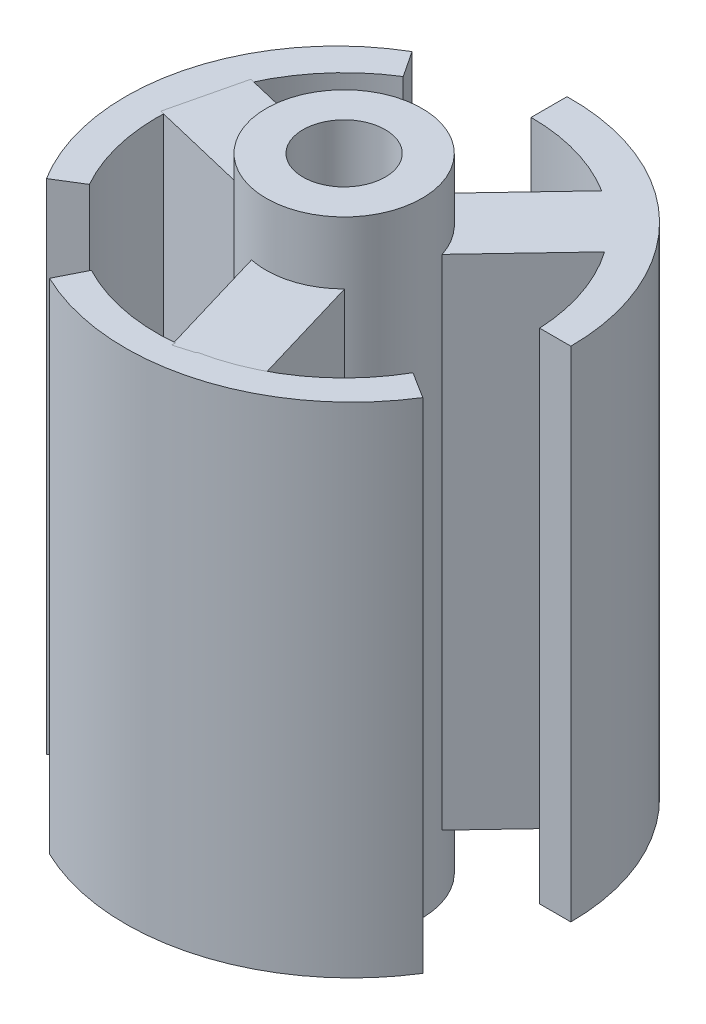
SolidWorks part; units mm, degrees
ref_plane "Front Plane" through (0, 0, 0) normal (0, 0, 1) x (1, 0, 0)
ref_plane "Top Plane" through (0, 0, 0) normal (0, 1, 0) x (1, 0, 0)
ref_plane "Right Plane" through (0, 0, 0) normal (1, 0, 0) x (0, 0, -1)
sketch "Sketch11" plane through (0, 0, 0) normal (0, 1, 0) x (1, 0, 0)
  line L0 (-15.1905, -8.6889) -> (0, 0.7002)
  line L1 (0, 0.7002) -> (-8.1366, -15.4934)
  line L2 (15.1201, -8.8109) -> (0, 0.7002)
  line L3 (0, 0.7002) -> (17.486, 0.7002)
  line L4 (0, 0.7002) -> (-9.3494, 14.7932)
  line L5 (0, 0.7002) -> (0, 17.8816)
  arc A3 (15.1201, -8.8109) -> (-8.1366, -15.4934) centre (-0.2456, 0.8547) cw
  arc A5 (-15.1905, -8.6889) -> (-9.3494, 14.7932) centre (-0.8078, 0.2009) cw
  arc A6 (17.486, 0.7002) -> (0, 17.8816) centre (0.3019, 0.7002) ccw
  point P11 (0, 0)
sketch "Sketch12" plane through (0, 0, 0) normal (0, 1, 0) x (1, 0, 0)
  circle A0 centre (0, 0) radius 15
extrude "Boss-Extrude6" add sketch "Sketch11" along normal blind 40 contours L0 A5 L4 | L2 A3 L1 | L3 A6 L5
extrude "Cut-Extrude9" cut sketch "Sketch12" along normal blind 40 contours A0
sketch "Sketch17" plane through (0, 0, 0) normal (0, 1, 0) x (1, 0, 0)
  line L0 (12.4951, 8.8245) -> (8.1399, 12.9515)
  line L1 (12.4951, 8.8245) -> (2.1256, -2.1183)
  line L2 (8.1399, 12.9515) -> (-2.2296, 2.0087)
  line L3 (2.1256, -2.1183) -> (-2.2296, 2.0087)
  line L4 (-2.8974, -0.7817) -> (2.8543, 0.9265)
  line L5 (1.3947, -15.2333) -> (-2.8974, -0.7817)
  line L6 (1.3947, -15.2333) -> (7.1464, -13.5251)
  line L7 (7.1464, -13.5251) -> (2.8543, 0.9265)
  line L8 (0.7717, 2.9) -> (-0.6248, -2.9352)
  line L9 (-13.8898, 6.4089) -> (0.7717, 2.9)
  line L10 (-13.8898, 6.4089) -> (-15.2863, 0.5736)
  line L11 (-15.2863, 0.5736) -> (-0.6248, -2.9352)
  arc A1 (14.9836, 0.7002) -> (0, 15) centre (0, 0) ccw construction
  point P18 (0, 0)
  dimension "D1" = 3
extrude "Boss-Extrude8" add sketch "Sketch17" along normal blind 40 separate body contours L2 L9 L8 L4 L7 L1 L0 | L4 L8 L3 L1 L7 | L9 L2 L3 L4 L8 | L11 L5 L6 L7 L1 L3 L8 | L5 L11 L8 L3 L4 | L10 L11 L5 L4 L3 L2 L9 | L4 L7 L6 L5 region at (5.7685, 0, -6.0874) region at (2.3876, 0, 8.0393) region at (1.914, 0, 0.4581) region at (-0.5603, 0, -1.8866) region at (-8.1561, 0, -1.9519) region at (-1.3537, 0, 1.4286)
sketch "Sketch18" plane through (0, 0, 0) normal (0, 1, 0) x (1, 0, 0)
  circle A0 centre (0, 0) radius 6.25
extrude "Boss-Extrude9" add sketch "Sketch18" along normal blind 45
extrude "Boss-Extrude10" add sketch "Sketch18<2>" against normal blind 5
sketch "Sketch18<2>" plane through (0, 0, 0) normal (0, 1, 0) x (1, 0, 0) same geometry as "Sketch18"
ref_plane "Plane1" through (0, -5, 0) normal (0, -1, 0) x (-1, 0, 0)
sketch "Sketch19" plane through (0, -5, 0) normal (0, -1, 0) x (-1, 0, 0)
  circle A0 centre (0, 0) radius 3.3
extrude "Cut-Extrude10" cut sketch "Sketch19" against normal blind 50
